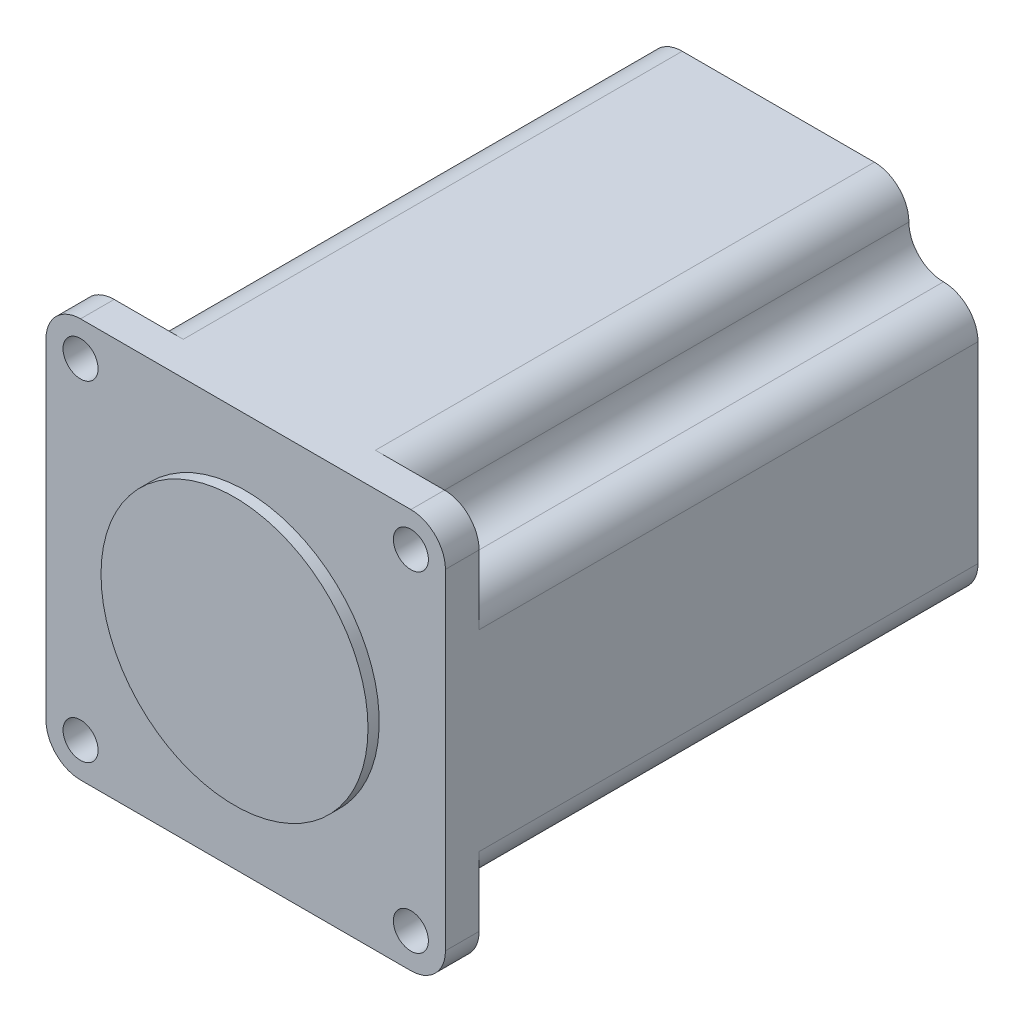
SolidWorks part; units mm, degrees
ref_plane "Front Plane" through (0, 0, 0) normal (0, 0, 1) x (1, 0, 0)
ref_plane "Top Plane" through (0, 0, 0) normal (0, 1, 0) x (1, 0, 0)
ref_plane "Right Plane" through (0, 0, 0) normal (1, 0, 0) x (0, 0, -1)
sketch "Sketch1" plane through (0, 0, 0) normal (0, 0, 1) x (1, 0, 0)
  line L1 (-28.5, -28.5) -> (28.5, -28.5)
  line L2 (-28.5, -28.5) -> (-28.5, 28.5)
  line L3 (-28.5, 28.5) -> (28.5, 28.5)
  line L4 (28.5, -28.5) -> (28.5, 28.5)
  line L5 (-28.5, -28.5) -> (28.5, 28.5) construction
  line L6 (-28.5, 28.5) -> (28.5, -28.5) construction
  point P0 (0, 0)
  dimension "D1" = 57
  dimension "D2" = 57
extrude "Boss-Extrude1" add sketch "Sketch1" against normal blind 76
sketch "Sketch3" plane through (0, 0, -76) normal (0, 0, -1) x (-1, 0, 0)
  line L0 (0, 28.5) -> (0, -28.5) construction
  line L1 (-28.5, 28.5) -> (28.5, 28.5) construction
  line L2 (28.5, -28.5) -> (-28.5, -28.5) construction
  line L3 (28.5, 0) -> (-28.5, 0) construction
  line L4 (28.5, 28.5) -> (28.5, -28.5) construction
  line L5 (-28.5, -28.5) -> (-28.5, 28.5) construction
  line L6 (-28.5, 23.57) -> (28.5, 23.57) construction
  line L7 (-28.5, -23.57) -> (28.5, -23.57) construction
  line L8 (23.57, 28.5) -> (23.57, -28.5) construction
  line L9 (-23.57, 28.5) -> (-23.57, -28.5) construction
  circle A0 centre (-23.57, 23.57) radius 2.5
  circle A1 centre (-23.57, -23.57) radius 2.5
  circle A2 centre (23.57, 23.57) radius 2.5
  circle A3 centre (23.57, -23.57) radius 2.5
  dimension "D5" = 5
  dimension "D6" = 5
  dimension "D7" = 5
  dimension "D8" = 5
  dimension "D1" = 23.57
  dimension "D2" = 23.57
  dimension "D3" = 23.57
  dimension "D4" = 23.57
extrude "Cut-Extrude1" cut sketch "Sketch3" against normal through all
sketch "Sketch4" plane through (0, 0, -76) normal (0, 0, -1) x (-1, 0, 0)
  line L0 (-28.5, 23.57) -> (-28.5, 28.5)
  line L1 (-28.5, 28.5) -> (-23.57, 28.5)
  line L2 (23.57, 28.5) -> (28.5, 28.5)
  line L3 (28.5, 28.5) -> (28.5, 23.57)
  line L4 (-28.5, -23.57) -> (-28.5, -28.5)
  line L5 (-28.5, -28.5) -> (-23.57, -28.5)
  line L6 (23.57, -28.5) -> (28.5, -28.5)
  line L7 (28.5, -28.5) -> (28.5, -23.57)
  arc A1 (-23.57, 28.5) -> (-28.5, 23.57) centre (-23.57, 23.57) ccw
  arc A2 (28.5, 23.57) -> (23.57, 28.5) centre (23.57, 23.57) ccw
  arc A3 (23.57, -28.5) -> (28.5, -23.57) centre (23.57, -23.57) ccw
  arc A4 (-28.5, -23.57) -> (-23.57, -28.5) centre (-23.57, -23.57) ccw
extrude "Cut-Extrude2" cut sketch "Sketch4" against normal through all
sketch "Sketch5" plane through (0, 0, -76) normal (0, 0, -1) x (-1, 0, 0)
  line L0 (-18.64, 23.57) -> (-18.64, -23.57) construction
  line L1 (-23.57, 18.64) -> (23.57, 18.64) construction
  line L2 (18.64, -23.57) -> (18.64, 23.57) construction
  line L3 (-23.57, -18.64) -> (23.57, -18.64) construction
  line L4 (-23.57, 28.5) -> (23.57, 28.5) construction
  line L5 (28.5, 23.57) -> (28.5, -23.57) construction
  line L6 (23.57, -28.5) -> (-23.57, -28.5) construction
  line L7 (-28.5, -23.57) -> (-28.5, 23.57) construction
  line L8 (-28.5, 13.71) -> (-28.5, -13.71)
  line L9 (-13.71, -28.5) -> (13.71, -28.5)
  line L10 (28.5, -13.71) -> (28.5, 13.71)
  line L11 (13.71, 28.5) -> (-13.71, 28.5)
  arc A0 (-23.57, 18.64) -> (-18.64, 23.57) centre (-23.57, 23.57) ccw
  arc A1 (-18.64, -23.57) -> (-23.57, -18.64) centre (-23.57, -23.57) ccw
  arc A2 (18.64, 23.57) -> (23.57, 18.64) centre (23.57, 23.57) ccw
  arc A3 (23.57, -18.64) -> (18.64, -23.57) centre (23.57, -23.57) ccw
  arc A4 (-18.64, 23.57) -> (-13.71, 28.5) centre (-13.71, 23.57) cw
  arc A5 (18.64, 23.57) -> (13.71, 28.5) centre (13.71, 23.57) ccw
  arc A6 (23.57, 18.64) -> (28.5, 13.71) centre (23.57, 13.71) cw
  arc A7 (-18.64, -23.57) -> (-13.71, -28.5) centre (-13.71, -23.57) ccw
  arc A8 (18.64, -23.57) -> (13.71, -28.5) centre (13.71, -23.57) cw
  arc A9 (-23.57, 18.64) -> (-28.5, 13.71) centre (-23.57, 13.71) ccw
  arc A10 (-23.57, -18.64) -> (-28.5, -13.71) centre (-23.57, -13.71) cw
  arc A11 (23.57, -18.64) -> (28.5, -13.71) centre (23.57, -13.71) ccw
extrude "Cut-Extrude3" cut sketch "Sketch5" against normal offset from surface (71.2 mm away) 4.8 flip side to cut up to face at (-26.07, -23.57, 0)
sketch "Sketch6" plane through (0, 0, 0) normal (0, 0, 1) x (1, 0, 0)
  circle A0 centre (0, 0) radius 19.05
  dimension "D1" = 38.1
extrude "Boss-Extrude2" add sketch "Sketch6" along normal blind 1.6
